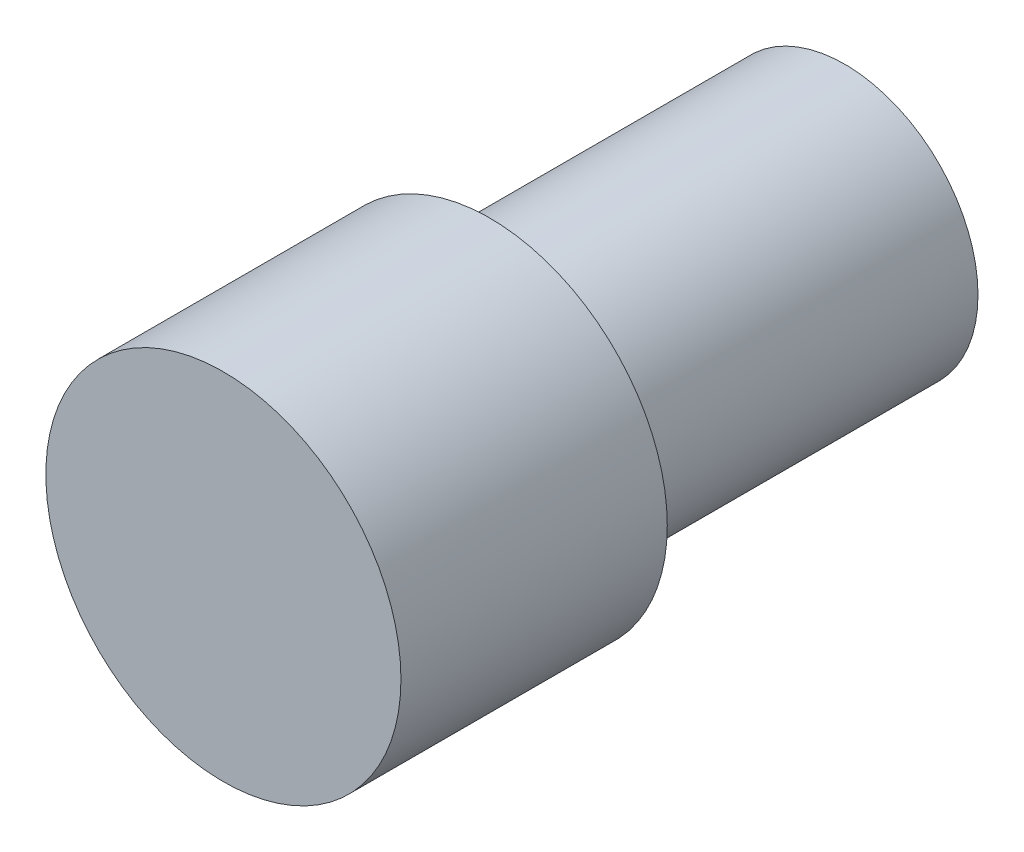
SolidWorks part; units mm, degrees
ref_plane "Front Plane" through (0, 0, 0) normal (0, 0, 1) x (1, 0, 0)
ref_plane "Top Plane" through (0, 0, 0) normal (0, 1, 0) x (1, 0, 0)
ref_plane "Right Plane" through (0, 0, 0) normal (1, 0, 0) x (0, 0, -1)
sketch "Sketch1" plane through (0, 0, 0) normal (0, 0, 1) x (1, 0, 0)
  circle A0 centre (0, 0) radius 2
  circle A1 centre (0, 0) radius 1.5
  dimension "D1" = 3
  dimension "D2" = 4
extrude "Boss-Extrude1" add sketch "Sketch1" along normal blind 3 contours A1 | A0 A1 region at (-1.9434, 0, 0) region at (0, 0, 0)
extrude "Boss-Extrude2" add sketch "Sketch1<3>" against normal blind 4 contours A1 region at (0, 0, 0)
sketch "Sketch1<3>" plane through (0, 0, 0) normal (0, 0, 1) x (1, 0, 0) same geometry as "Sketch1"
